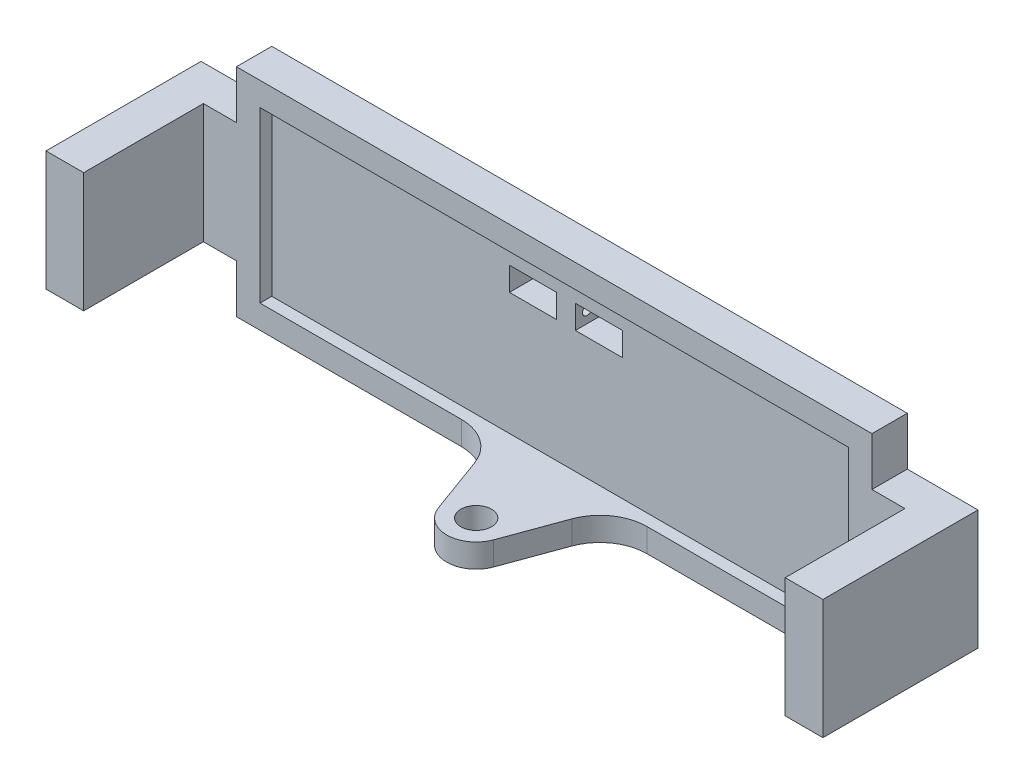
SolidWorks part; units mm, degrees
ref_plane "Front Plane" through (0, 0, 0) normal (0, 0, 1) x (1, 0, 0)
ref_plane "Top Plane" through (0, 0, 0) normal (0, 1, 0) x (1, 0, 0)
ref_plane "Right Plane" through (0, 0, 0) normal (1, 0, 0) x (0, 0, -1)
sketch "Sketch1" plane through (0, 0, 0) normal (0, 0, 1) x (1, 0, 0)
  line L0 (-62.415, 17.965) -> (62.415, 17.965)
  line L1 (-61.915, 17.465) -> (61.915, 17.465) construction
  line L2 (-61.915, 17.465) -> (-61.915, -17.465) construction
  line L3 (-61.915, -17.465) -> (61.915, -17.465) construction
  line L4 (61.915, 17.465) -> (61.915, -17.465) construction
  line L5 (-61.915, 17.465) -> (61.915, -17.465) construction
  line L6 (-61.915, -17.465) -> (61.915, 17.465) construction
  line L7 (62.415, 17.965) -> (62.415, -17.965)
  line L8 (-62.415, -17.965) -> (62.415, -17.965)
  line L9 (-62.415, 17.965) -> (-62.415, -17.965)
  line L10 (-67.415, 22.965) -> (67.415, 22.965)
  line L11 (67.415, 22.965) -> (67.415, -22.965)
  line L12 (-67.415, -22.965) -> (67.415, -22.965)
  line L13 (-67.415, 22.965) -> (-67.415, -22.965)
  point P0 (0, 0)
  dimension "D2" = 34.93
  dimension "D1" = 123.83
  dimension "D3" = 0.5
  dimension "D4" = 5
extrude "Boss-Extrude1" add sketch "Sketch1" along normal mid plane 5 contours L10 L13 L12 L11 L9 L0 L7 L8 | L0 L9 L8 L7 | L0 L7 L8 L9 | L10 L11 L12 L13 region at (0, 0, 0) region at (0, 21.5406, 0)
extrude "Boss-Extrude2" add sketch "Sketch1<3>" along normal mid plane 5 from surface starting at face at (0, 0, 2.5)
sketch "Sketch1<3>" plane through (0, 0, 0) normal (0, 0, 1) x (1, 0, 0) same geometry as "Sketch1"
sketch "Sketch2" plane through (0, -22.965, 0) normal (0, -1, 0) x (1, 0, 0)
  line L0 (-67.415, 2.5) -> (67.415, 2.5) construction
  line L1 (-67.415, 5) -> (-67.415, -2.5) construction
  line L2 (67.415, 5) -> (67.415, -2.5) construction
  line L5 (67.415, 5) -> (-67.415, 5) construction
  line L7 (0, 2.5) -> (0, 21.55) construction
  line L8 (-5.8705, 23.6946) -> (-12.7, 5)
  line L9 (-12.7, 5) -> (12.7, 5)
  line L10 (5.8705, 23.6946) -> (12.7, 5)
  circle A0 centre (0, 21.55) radius 3.25
  circle A1 centre (0, 21.55) radius 6.25
  point P18 (0, 5)
  line M10 (67.415, 5) -> (-67.415, 5)
  dimension "D3" = 6.5
  dimension "D1" = 2.5
  dimension "D2" = 19.05
  dimension "D5" = 12.7
  dimension "D4" = 3
extrude "Boss-Extrude3" add sketch "Sketch2" against normal up to surface (5 mm away) contours A1 L8 L10 M10 | A1 A0 region at (0, -22.965, 10.9023) region at (0, -22.965, 27.6232) up to face at (0, -17.965, 3.75)
fillet "Fillet1" radius 10 2 edges at (-12.7, -20.465, 5) (12.7, -20.465, 5)
sketch "Sketch5" plane through (0, 0, -2.5) normal (0, 0, -1) x (-1, 0, 0)
  line L0 (0, 22.965) -> (0, -22.965) construction
  line L1 (67.415, 22.965) -> (-67.415, 22.965) construction
  line L2 (67.415, -22.965) -> (-67.415, -22.965) construction
  line L3 (12, 7.965) -> (2, 7.965)
  line L4 (-12, 12.965) -> (-2, 12.965)
  line L5 (-12, 12.965) -> (-12, 7.965)
  line L6 (-12, 7.965) -> (-2, 7.965)
  line L7 (-2, 12.965) -> (-2, 7.965)
  line L8 (-12, 12.965) -> (-2, 7.965) construction
  line L9 (-12, 7.965) -> (-2, 12.965) construction
  line L10 (2, 12.965) -> (2, 7.965)
  line L11 (12, 12.965) -> (2, 12.965)
  line L12 (12, 12.965) -> (12, 7.965)
  point P6 (-7, 10.465)
  dimension "D1" = 5
  dimension "D2" = 10
  dimension "D3" = 2
  dimension "D4" = 10
extrude "Cut-Extrude4" cut sketch "Sketch5" against normal through all both and the other way through all
sketch "Sketch6" plane through (-2, 0, 0) normal (-1, 0, 0) x (0, 0, 1)
  line L0 (2.5, 12.965) -> (-2.5, 7.965) construction
  line L4 (-2.5, 7.965) -> (2.5, 7.965)
  line L5 (2.5, 7.965) -> (2.5, 12.965)
  line L6 (2.5, 12.965) -> (-2.5, 12.965)
  line L7 (-2.5, 12.965) -> (-2.5, 7.965)
  line L8 (-2.5, 7.965) -> (2.5, 7.965) construction
  line L9 (2.5, 7.965) -> (2.5, 12.965) construction
  line L10 (2.5, 12.965) -> (-2.5, 12.965) construction
  line L11 (-2.5, 12.965) -> (-2.5, 7.965) construction
  circle A0 centre (0, 10.465) radius 1
  dimension "D2" = 2
  dimension "D1" = 0
extrude "Cut-Extrude5" cut sketch "Sketch6" against normal up to next from surface starting at face at (-2, 10.465, 0)
sketch "Sketch7" plane through (0, 0, -2.5) normal (0, 0, -1) x (-1, 0, 0)
  line L0 (0, 22.965) -> (0, 0) construction
  line L1 (-82.415, 12.7) -> (-74.415, 12.7)
  line L2 (-82.415, 12.7) -> (-82.415, -12.7)
  line L3 (-82.415, -12.7) -> (-74.415, -12.7)
  line L4 (-74.415, 12.7) -> (-74.415, -12.7)
  line L5 (-82.415, 12.7) -> (-74.415, -12.7) construction
  line L6 (-82.415, -12.7) -> (-74.415, 12.7) construction
  line L7 (67.415, 22.965) -> (-67.415, 22.965) construction
  line L8 (0, 0) -> (-67.415, 0) construction
  line L9 (-67.415, 22.965) -> (-67.415, -22.965) construction
  line L10 (-74.415, 12.7) -> (-67.415, 12.7)
  line L11 (-67.415, 12.7) -> (-67.415, -12.7)
  line L12 (-67.415, -12.7) -> (-74.415, -12.7)
  line L13 (67.415, -12.7) -> (74.415, -12.7)
  line L14 (67.415, 12.7) -> (67.415, -12.7)
  line L15 (74.415, 12.7) -> (67.415, 12.7)
  line L16 (82.415, -12.7) -> (74.415, -12.7)
  line L17 (74.415, 12.7) -> (74.415, -12.7)
  line L18 (82.415, 12.7) -> (74.415, 12.7)
  line L19 (82.415, 12.7) -> (82.415, -12.7)
  point P0 (-78.415, 0)
  line M16 (-67.415, 22.965) -> (-67.415, -22.965)
  line M18 (67.415, -22.965) -> (67.415, 22.965)
  dimension "D1" = 15
  dimension "D2" = 8
  dimension "D3" = 25.4
extrude "Boss-Extrude4" add sketch "Sketch7" against normal up to surface (7.5 mm away) contours L12 L10 L4 M16 | L4 L1 L2 L3 | L19 L18 L17 L16 | L17 L15 L13 M18 region at (78.415, 0, -2.5) region at (70.915, 0, -2.5) region at (-70.915, 0, -2.5) region at (-78.415, 0, -2.5) up to face at (0, -6.8217, 5)
extrude "Boss-Extrude5" add sketch "Sketch7<4>" against normal blind 25.4 from surface contours L4 L1 L2 L3 | L19 L18 L17 L16 region at (78.415, 0, -2.5) region at (-78.415, 0, -2.5) starting at face at (0, -4.093, 5)
sketch "Sketch7<4>" plane through (0, 0, -2.5) normal (0, 0, -1) x (-1, 0, 0) same geometry as "Sketch7"
equation "\"CamWidth\"= 123.83"
equation "\"CamHeight\"= 34.93"
equation "\"D2@Sketch1\"=\"CamHeight\""
equation "\"D1@Sketch1\"=\"CamWidth\""
equation "\"CamWraparound\"= 5"
equation "\"CamOffset\"= 0.5"
equation "\"D3@Sketch1\"=\"CamOffset\""
equation "\"Face2Face\"= 15mm"
equation "\"D1@Sketch7\"=\"Face2Face\""
equation "\"ArmThickness\"= 8mm"
equation "\"D2@Sketch7\"=\"ArmThickness\""
